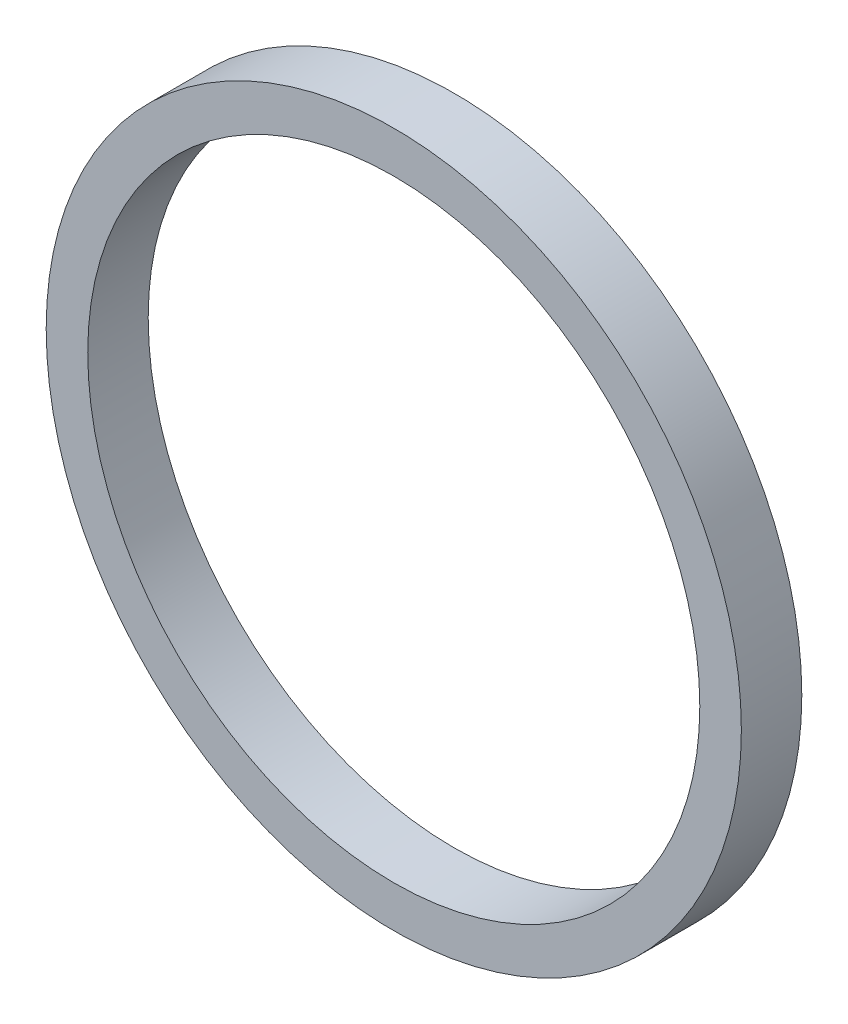
SolidWorks part; units mm, degrees
ref_plane "Front Plane" through (0, 0, 0) normal (0, 0, 1) x (1, 0, 0)
ref_plane "Top Plane" through (0, 0, 0) normal (0, 1, 0) x (1, 0, 0)
ref_plane "Right Plane" through (0, 0, 0) normal (1, 0, 0) x (0, 0, -1)
sketch "Sketch1" plane through (0, 0, 0) normal (0, 0, 1) x (1, 0, 0)
  circle A0 centre (0, 0) radius 5.0625
  circle A1 centre (0, 0) radius 5.75
  dimension "D1" = 10.125
  dimension "D2" = 11.5
extrude "Boss-Extrude1" add sketch "Sketch1" along normal blind 1
equation "\"RingPinShaft\"= 5"
equation "\"CenterBearingOut\"=32"
equation "\"RingPostIn\"=5"
equation "\"CamBearingOut\"=15.15"
equation "\"DiskOutputShaft\"=10"
equation "\"CenterShaft\"=25"
equation "\"Eccentricity\"=2"
equation "\"CycCamShaft\"=10"
equation "\"D1@Sketch1\"=\"CycCamShaft\" + 0.125"
equation "\"D2@Sketch1\"=\"CycCamShaft\"+1.5"
